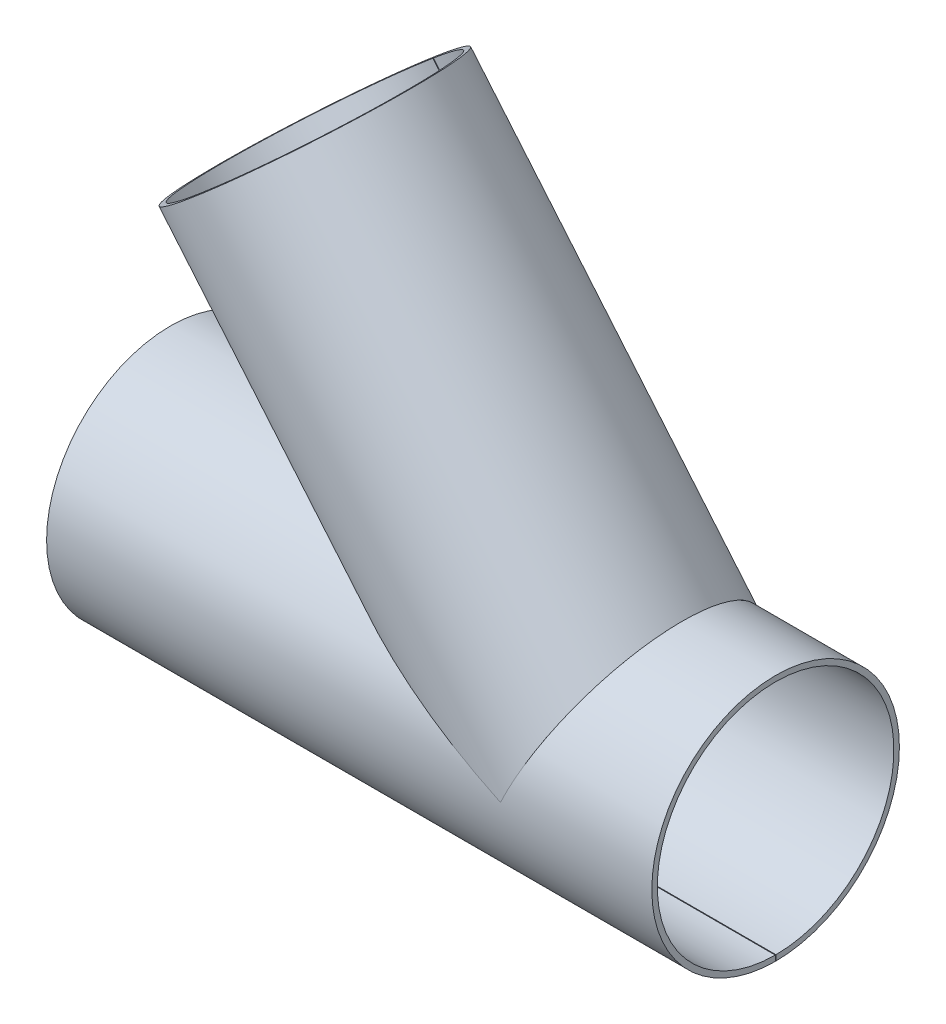
SolidWorks part; units mm, degrees
ref_plane "前视基准面" through (0, 0, 0) normal (0, 0, 1) x (1, 0, 0)
ref_plane "上视基准面" through (0, 0, 0) normal (0, 1, 0) x (1, 0, 0)
ref_plane "右视基准面" through (0, 0, 0) normal (1, 0, 0) x (0, 0, -1)
sketch "草图1" plane through (0, 0, 0) normal (0, 0, 1) x (1, 0, 0)
  line L0 (-660, 0) -> (220, 0) construction
  line L1 (-449.9513, 536.2311) -> (0, 0) construction
  line L2 (220, 180) -> (220, -180) construction
  line L3 (-312.0633, 651.9329) -> (-587.8393, 420.5293) construction
  line L4 (220, 0) -> (228, 0) construction
  line L5 (-312.0633, 651.9329) -> (83.9354, 180) construction
  line L6 (83.9354, 180) -> (220, 180) construction
  line L7 (0, 0) -> (83.9354, 180) construction
  line L8 (-587.8393, 420.5293) -> (-386.0112, 180) construction
  line L9 (-386.0112, 180) -> (-660, 180) construction
  line L10 (-660, 180) -> (-660, -180) construction
  line L11 (-386.0112, 180) -> (0, 0) construction
  line L12 (0, 0) -> (-449.9513, 536.2311)
  dimension "β" = 50
  dimension "d" = 360
  dimension "l" = 880
  dimension "c" = 700
  dimension "b" = 660
  dimension "t" = 8
sketch "草图2" plane through (0, 0, 0) normal (1, 0, 0) x (0, 0, -1)
  circle A0 centre (0, 0) radius 180
extrude "拉伸-薄壁1" add sketch "草图2" along normal up to vertex (220 mm away) and the other way up to vertex (660 mm away) thin up to point (220, -180, 0) other way up to point (-660, 0, 0) thin type one direction reverse wall 8
ref_plane "基准面1" through (-449.9513, 536.2311, 0) normal (0.6428, -0.766, 0) x (0.766, 0.6428, 0)
sketch "草图3" plane through (-449.9513, 536.2311, 0) normal (0.6428, -0.766, 0) x (0.766, 0.6428, 0)
  circle A0 centre (0, 0) radius 180
extrude "拉伸-薄壁2" add sketch "草图3" along normal up to vertex (700 mm away) separate body thin up to point (0, 0, 0) thin type one direction reverse wall 8
sketch "草图4" plane through (0, 0, 0) normal (0, 0, 1) x (1, 0, 0)
  line L0 (-386.0112, 180) -> (0, 0) construction
  line L1 (0, 0) -> (83.9354, 180) construction
  line L2 (-312.0633, 651.9329) -> (83.9354, 180) construction
  line L3 (-587.8393, 420.5293) -> (-386.0112, 180) construction
  line L4 (-312.0633, 651.9329) -> (-587.8393, 420.5293) construction
  line L5 (-386.0112, 180) -> (0, 0)
  line L6 (0, 0) -> (83.9354, 180)
  line L7 (-312.0633, 651.9329) -> (83.9354, 180)
  line L8 (-587.8393, 420.5293) -> (-386.0112, 180)
  line L9 (-312.0633, 651.9329) -> (-587.8393, 420.5293)
extrude "切除-拉伸1" cut sketch "草图4" against normal through all and the other way through all flip side to cut
extrude "切除-拉伸2" cut sketch "草图4<2>" against normal through all and the other way through all
sketch "草图4<2>" plane through (0, 0, 0) normal (0, 0, 1) x (1, 0, 0) same geometry as "草图4"
sketch "草图5" plane through (0, 0, 0) normal (0, 1, 0) x (1, 0, 0)
  line L0 (-660, 0) -> (220, 0) construction
  line L1 (-660, 0) -> (220, 0)
extrude "切除-拉伸-薄壁1" cut sketch "草图5" against normal through all thin thin type mid plane wall 1
extrude "切除-拉伸-薄壁2" cut sketch "草图1" against normal through all thin thin type mid plane wall 1
equation "\"D5@拉伸-薄壁1\" = \"t@草图1\""
equation "\"D5@拉伸-薄壁2\" = \"t@草图1\""
